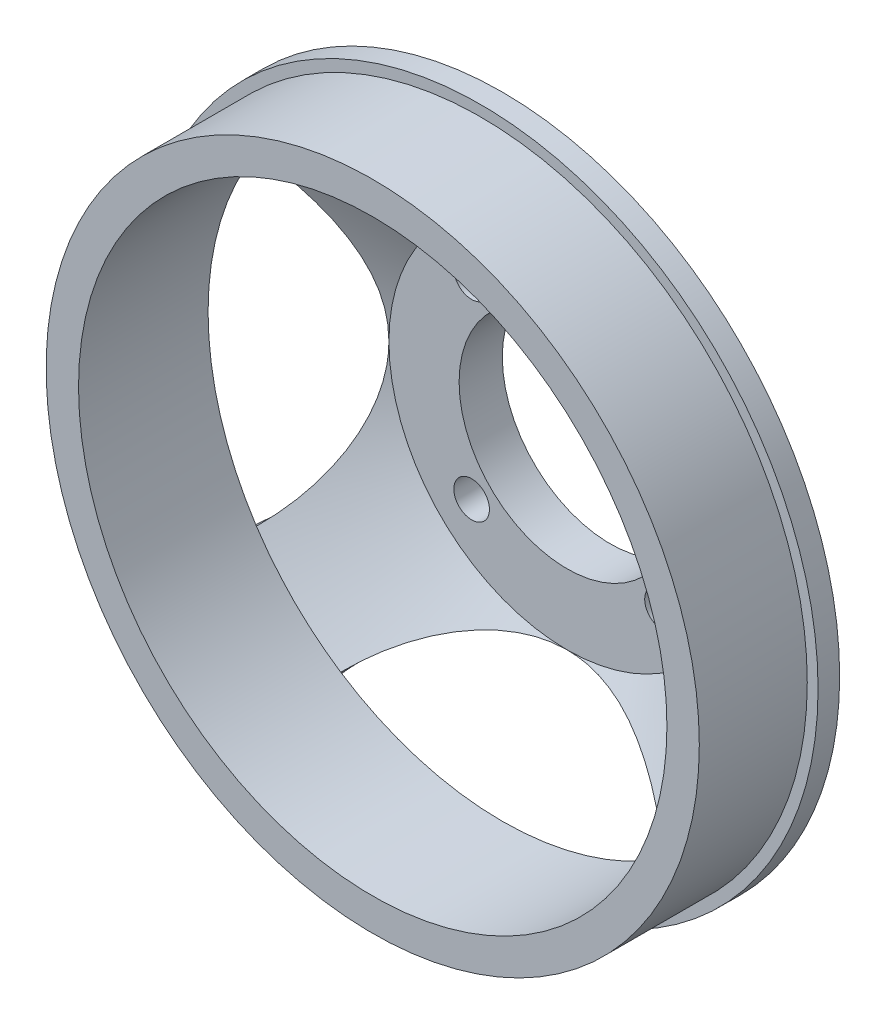
SolidWorks part; units mm, degrees
ref_plane "Front Plane" through (0, 0, 0) normal (0, 0, 1) x (1, 0, 0)
ref_plane "Top Plane" through (0, 0, 0) normal (0, 1, 0) x (1, 0, 0)
ref_plane "Right Plane" through (0, 0, 0) normal (1, 0, 0) x (0, 0, -1)
sketch "Sketch1" plane through (0, 0, 0) normal (0, 0, 1) x (1, 0, 0)
  circle A0 centre (0, 0) radius 31.25
  circle A1 centre (0, 0) radius 27.25
  circle A2 centre (0, 0) radius 29.25
  dimension "D1" = 62.5
  dimension "D2" = 4
  dimension "D3" = 2
extrude "Boss-Extrude2" add sketch "Sketch1" along normal blind 12 contours A0 A2 | A2 A1 region at (-30.3661, 0, 0) region at (-28.4227, 0, 0)
ref_plane "Plane1" through (0, 0, -10) normal (0, 0, -1) x (-1, 0, 0)
sketch "Sketch7" plane through (0, 0, -10) normal (0, 0, -1) x (-1, 0, 0)
  line L0 (0, 16.5) -> (16.5, 0) construction
  line L1 (0, 0) -> (22.0971, 22.0971) construction
  line L2 (0, 0) -> (-22.0971, -22.0971) construction
  line L3 (-16.5, 0) -> (0, 16.5) construction
  line L4 (0, 0) -> (-22.0971, 22.0971) construction
  line L5 (0, 0) -> (22.0971, -22.0971) construction
  circle A0 centre (0, 0) radius 16.5
  circle A1 centre (0, 0) radius 10
  arc A3 (25.8908, 17.4993) -> (16.5, 0) centre (37.5, 0) ccw
  arc A6 (0, 16.5) -> (17.4993, 25.8908) centre (0, 37.5) ccw
  arc A7 (16.5, 0) -> (25.8908, -17.4993) centre (37.5, 0) ccw
  arc A10 (25.8908, 17.4993) -> (17.4993, 25.8908) centre (0, 0) ccw
  arc A11 (17.4993, -25.8908) -> (25.8908, -17.4993) centre (0, 0) ccw
  arc A12 (17.4993, -25.8908) -> (0, -16.5) centre (0, -37.5) ccw
  arc A13 (0, -16.5) -> (-17.4993, -25.8908) centre (0, -37.5) ccw
  arc A14 (-25.8908, -17.4993) -> (-17.4993, -25.8908) centre (0, 0) ccw
  arc A15 (-25.8908, -17.4993) -> (-16.5, 0) centre (-37.5, 0) ccw
  arc A16 (-16.5, 0) -> (-25.8908, 17.4993) centre (-37.5, 0) ccw
  arc A17 (-17.4993, 25.8908) -> (-25.8908, 17.4993) centre (0, 0) ccw
  arc A18 (-17.4993, 25.8908) -> (0, 16.5) centre (0, 37.5) ccw
  circle A19 centre (0, 0) radius 14.5
  circle A20 centre (0, 0) radius 12.5 construction
  point P9 (-8.8388, 8.8388)
  point P12 (0, 16.5)
  point P33 (0, 0)
  point P34 (8.8388, 8.8388)
  point P35 (-8.8388, -8.8388)
  point P36 (8.8388, -8.8388)
  dimension "D1" = 33
  dimension "D2" = 20
  dimension "D3" = 31.25
  dimension "D4" = 21
  dimension "D5" = 21
  dimension "D6" = 29
  dimension "D8" = 25
  dimension "D7" = 4
extrude "Boss-Extrude6" add sketch "Sketch7" against normal blind 4 separate body contours A0 A19 | A19 A1 region at (-11.3373, -11.3373, -10) region at (14.0899, 0, -10)
sketch "Sketch1<9>" plane through (0, 0, 0) normal (0, 0, 1) x (1, 0, 0) same geometry as "Sketch1"
sketch "Sketch7<14>" plane through (0, 0, -10) normal (0, 0, -1) x (-1, 0, 0) same geometry as "Sketch7"
sketch "Sketch10" plane through (0, 0, 0) normal (0, 1, 0) x (1, 0, 0)
  line L1 (-27.25, 0) -> (-31.25, 0)
  line L4 (0, 0) -> (0, 15.4328) construction
  line L6 (-16.5, 10) -> (-16.5, 6) construction
  line L7 (-16.5, 10) -> (-16.5, 6)
  line L10 (-16.5, 10) -> (-31.25, 0)
  line L11 (-16.5, 6) -> (-27.25, 0)
  dimension "D1" = 12.3111
sketch "Sketch11" plane through (0, 0, 0) normal (1, 0, 0) x (0, 0, -1)
  line L0 (-21.7079, 0) -> (10, 0) construction
revolve "Revolve1" add sketch "Sketch10" angle 360 about L4 region at (-22.4528, 0, -4.3695)
extrude "Cut-Extrude3" cut sketch "Sketch7<16>" against normal blind 10 flip side to cut contours A16 A17 A18 A6 A10 A3 A7 A11 A12 A13 A14 A15
sketch "Sketch7<16>" plane through (0, 0, -10) normal (0, 0, -1) x (-1, 0, 0) same geometry as "Sketch7"
hole_wizard "M4x0.7 Tapped Hole1" positions "Sketch18" profile "Sketch19" tap size "M4x0.7" standard "ANSI Metric" end condition through all
sketch "Sketch18" plane through (0, 0, -10) normal (0, 0, -1) x (-1, 0, 0)
  point P0 (-8.8388, 8.8388)
  point P3 (8.8388, 8.8388)
  point P6 (8.8388, -8.8388)
  point P9 (-8.8388, -8.8388)
sketch "Sketch19" plane through (8.8388, 8.8388, -10) normal (1, 0, 0) x (0, 1, 0)
  line L0 (0, 0) -> (0, 22)
  line L1 (0, 22) -> (1.65, 22)
  line L2 (1.65, 22) -> (1.65, 0)
  line L5 (1.65, 0) -> (0, 0)
  line L11 (0, -6.35) -> (0, 107.95) construction
  dimension "Thru Tap Drill Dia." = 3.3
  dimension "Thru Tap Drill Depth" = 22
cosmetic thread "Hole Thread1" parameters "D2"=4
cosmetic thread "Hole Thread2" parameters "D2"=4
cosmetic thread "Hole Thread3" parameters "D2"=4
cosmetic thread "Hole Thread4" parameters "D2"=4
sketch "Sketch20" plane through (0, 0, 12) normal (0, 0, 1) x (1, 0, 0)
  circle A2 centre (0, 0) radius 31.25 construction
  circle A3 centre (0, 0) radius 30.25
  circle A4 centre (0, 0) radius 30.25
  circle A5 centre (0, 0) radius 31.25
  dimension "D1" = 1
extrude "Cut-Extrude4" cut sketch "Sketch20" against normal blind 10
